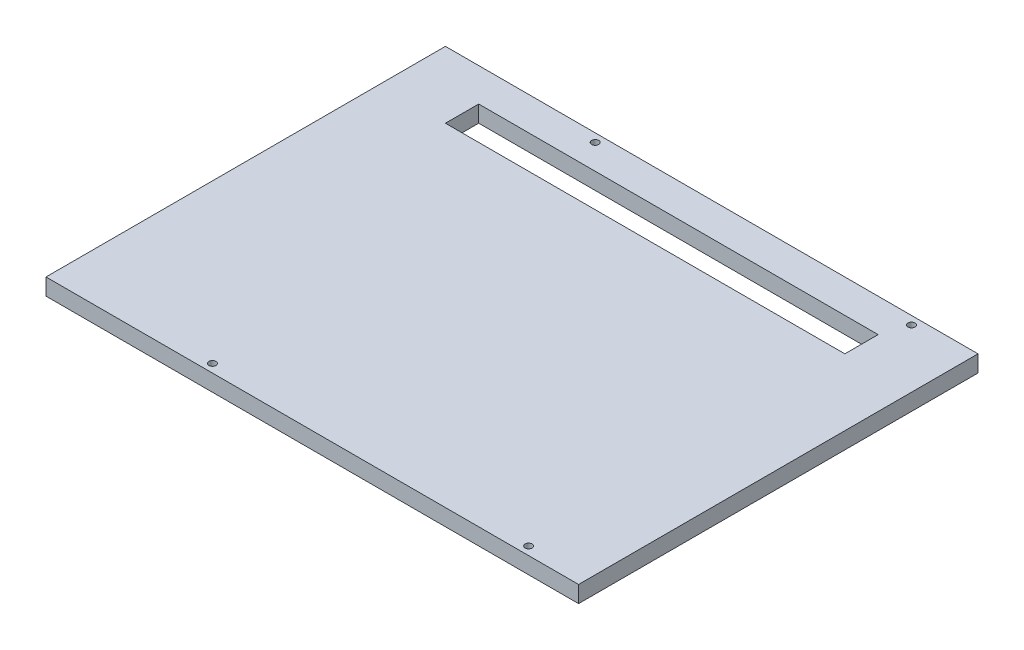
SolidWorks part; units mm, degrees
ref_plane "Front Plane" through (0, 0, 0) normal (0, 0, 1) x (1, 0, 0)
ref_plane "Top Plane" through (0, 0, 0) normal (0, 1, 0) x (1, 0, 0)
ref_plane "Right Plane" through (0, 0, 0) normal (1, 0, 0) x (0, 0, -1)
sketch "Sketch2" plane through (0, 0, 0) normal (0, 1, 0) x (1, 0, 0)
  line L1 (-101.6, -76.2) -> (101.6, -76.2)
  line L2 (-101.6, -76.2) -> (-101.6, 76.2)
  line L3 (-101.6, 76.2) -> (101.6, 76.2)
  line L4 (101.6, -76.2) -> (101.6, 76.2)
  line L5 (-101.6, -76.2) -> (101.6, 76.2) construction
  line L6 (-101.6, 76.2) -> (101.6, -76.2) construction
  point P0 (0, 0)
  dimension "D1" = 203.2
  dimension "D2" = 152.4
extrude "Boss-Extrude1" add sketch "Sketch2" along normal blind 6.35
sketch "Sketch3" plane through (0, 6.35, 0) normal (0, 1, 0) x (1, 0, 0)
  line L0 (-101.6, 0) -> (101.6, 0) construction
  line L1 (-101.6, 76.2) -> (-101.6, -76.2) construction
  line L2 (101.6, -76.2) -> (101.6, 76.2) construction
  line L3 (0, 76.2) -> (0, -76.2) construction
  line L4 (101.6, 76.2) -> (-101.6, 76.2) construction
  line L5 (-101.6, -76.2) -> (101.6, -76.2) construction
  line L7 (-76.2, 63.5) -> (76.2, 63.5)
  line L8 (-76.2, 63.5) -> (-76.2, 50.8)
  line L9 (-76.2, 50.8) -> (76.2, 50.8)
  line L10 (76.2, 63.5) -> (76.2, 50.8)
  line L11 (-76.2, 63.5) -> (76.2, 50.8) construction
  line L12 (-76.2, 50.8) -> (76.2, 63.5) construction
  point P12 (0, 57.15)
  dimension "D1" = 12.7
  dimension "D2" = 152.4
  dimension "D3" = 12.7
extrude "Cut-Extrude1" cut sketch "Sketch3" against normal blind 6.35
sketch "Sketch4" plane through (0, 0, 0) normal (0, -1, 0) x (1, 0, 0)
  line L0 (-101.6, -76.2) -> (-101.6, 76.2) construction
  line L1 (-101.6, 50.8) -> (-76.2, 50.8)
  line L2 (-101.6, 50.8) -> (-101.6, 25.4)
  line L3 (-101.6, 25.4) -> (-76.2, 25.4)
  line L4 (-76.2, 50.8) -> (-76.2, 25.4)
  line L5 (0, 76.2) -> (0, -76.2) construction
  line L6 (-101.6, 76.2) -> (101.6, 76.2) construction
  line L7 (101.6, -76.2) -> (-101.6, -76.2) construction
  line L8 (-101.6, 0) -> (101.6, 0) construction
  line L9 (101.6, 76.2) -> (101.6, -76.2) construction
  line L10 (101.6, 25.4) -> (76.2, 25.4)
  line L11 (76.2, 50.8) -> (76.2, 25.4)
  line L12 (101.6, 50.8) -> (76.2, 50.8)
  line L13 (101.6, 50.8) -> (101.6, 25.4)
  line L14 (101.6, -50.8) -> (101.6, -25.4)
  line L15 (101.6, -50.8) -> (76.2, -50.8)
  line L16 (76.2, -50.8) -> (76.2, -25.4)
  line L17 (101.6, -25.4) -> (76.2, -25.4)
  line L18 (-101.6, -25.4) -> (-76.2, -25.4)
  line L19 (-76.2, -50.8) -> (-76.2, -25.4)
  line L20 (-101.6, -50.8) -> (-76.2, -50.8)
  line L21 (-101.6, -50.8) -> (-101.6, -25.4)
  dimension "D1" = 25.4
  dimension "D2" = 25.4
  dimension "D3" = 25.4
sketch "Sketch6" plane through (0, 0, 0) normal (0, -1, 0) x (1, 0, 0)
  line L0 (0, -50.8) -> (0, -63.5) construction
  line L1 (-76.2, -50.8) -> (76.2, -50.8) construction
  line L2 (76.2, -63.5) -> (-76.2, -63.5) construction
sketch "Sketch7" plane through (-101.6, 0, 0) normal (-1, 0, 0) x (0, 0, 1)
  line L0 (-38.1, -25.4) -> (-38.1, 6.35) construction
  line L1 (-25.4, -25.4) -> (-50.8, -25.4) construction
  line L2 (-76.2, 6.35) -> (76.2, 6.35) construction
  line L3 (-50.8, -12.7) -> (-25.4, -12.7) construction
  line L4 (-50.8, -25.4) -> (-50.8, 0) construction
  line L5 (-25.4, -25.4) -> (-25.4, 0) construction
  line L6 (38.1, -25.4) -> (38.1, 6.35) construction
  line L7 (50.8, -25.4) -> (25.4, -25.4) construction
  line L8 (25.4, -12.7) -> (50.8, -12.7) construction
  line L9 (25.4, -25.4) -> (25.4, 0) construction
  line L10 (50.8, -25.4) -> (50.8, 0) construction
  circle A0 centre (-38.1, -12.7) radius 6.35
  circle A1 centre (38.1, -12.7) radius 6.35
  dimension "D1" = 12.7
  dimension "D2" = 12.7
sketch "Sketch8" plane through (101.6, 0, 0) normal (1, 0, 0) x (0, 0, -1)
  line L0 (-50.8, -12.7) -> (50.8, -12.7) construction
  line L1 (-50.8, -25.4) -> (-50.8, 0) construction
  line L2 (50.8, -25.4) -> (50.8, 0) construction
  line L3 (-38.1, -25.4) -> (-38.1, 6.35) construction
  line L4 (50.8, -25.4) -> (25.4, -25.4) construction
  line L5 (38.1, -25.4) -> (38.1, 6.35) construction
  line L6 (-76.2, 6.35) -> (76.2, 6.35) construction
  line L7 (-25.4, -25.4) -> (-50.8, -25.4) construction
  circle A0 centre (-38.1, -12.7) radius 6.35
  circle A1 centre (38.1, -12.7) radius 6.35
  dimension "D1" = 12.7
  dimension "D2" = 12.7
ref_plane "Plane1" through (0, 0, 0) normal (-1, 0, 0) x (0, 0, 1)
sketch "Sketch12" plane through (0, 6.35, 0) normal (0, 1, 0) x (1, 0, 0)
  line L0 (101.6, 76.2) -> (-101.6, 76.2) construction
  line L1 (-38.1204, 76.2) -> (25.3796, 76.2)
  line L2 (-38.1204, 76.2) -> (-38.1204, 63.5)
  line L3 (-38.1204, 63.5) -> (25.3796, 63.5)
  line L4 (25.3796, 76.2) -> (25.3796, 63.5)
  line L5 (76.2, 63.5) -> (-76.2, 63.5) construction
  dimension "D1" = 63.5
hole_wizard "#6-32 Tapped Hole1" positions "Sketch13" profile "Sketch14" tap size "#6-32" standard "ANSI Inch"
sketch "Sketch13" plane through (0, 6.35, 0) normal (0, 1, 0) x (1, 0, 0)
  point P12 (-41.275, -73.025)
  point P15 (-41.275, 73.025)
  point P18 (79.375, 73.025)
  point P21 (79.375, -73.025)
cosmetic thread "Hole Thread6" parameters "D1"=11.43, "D2"=3.5052
cosmetic thread "Hole Thread7" parameters "D1"=11.43, "D2"=3.5052
cosmetic thread "Hole Thread8" parameters "D1"=11.43, "D2"=3.5052
cosmetic thread "Hole Thread9" parameters "D1"=11.43, "D2"=3.5052
sketch "Sketch14" plane through (-41.275, 6.35, 73.025) normal (1, 0, 0) x (0, 0, 1)
  line L0 (0, 0) -> (0, 13.5127)
  line L1 (0, 13.5127) -> (1.3525, 12.7)
  line L2 (1.3525, 12.7) -> (1.3525, 0)
  line L5 (1.3525, 0) -> (0, 0)
  line L10 (0, 13.5127) -> (-1.3526, 12.7) construction
  line L11 (0, -6.35) -> (0, 107.95) construction
  dimension "Tap Drill Dia." = 2.7051
  dimension "Tap Drill Depth" = 12.7
  dimension "Drill Angle" = 118
